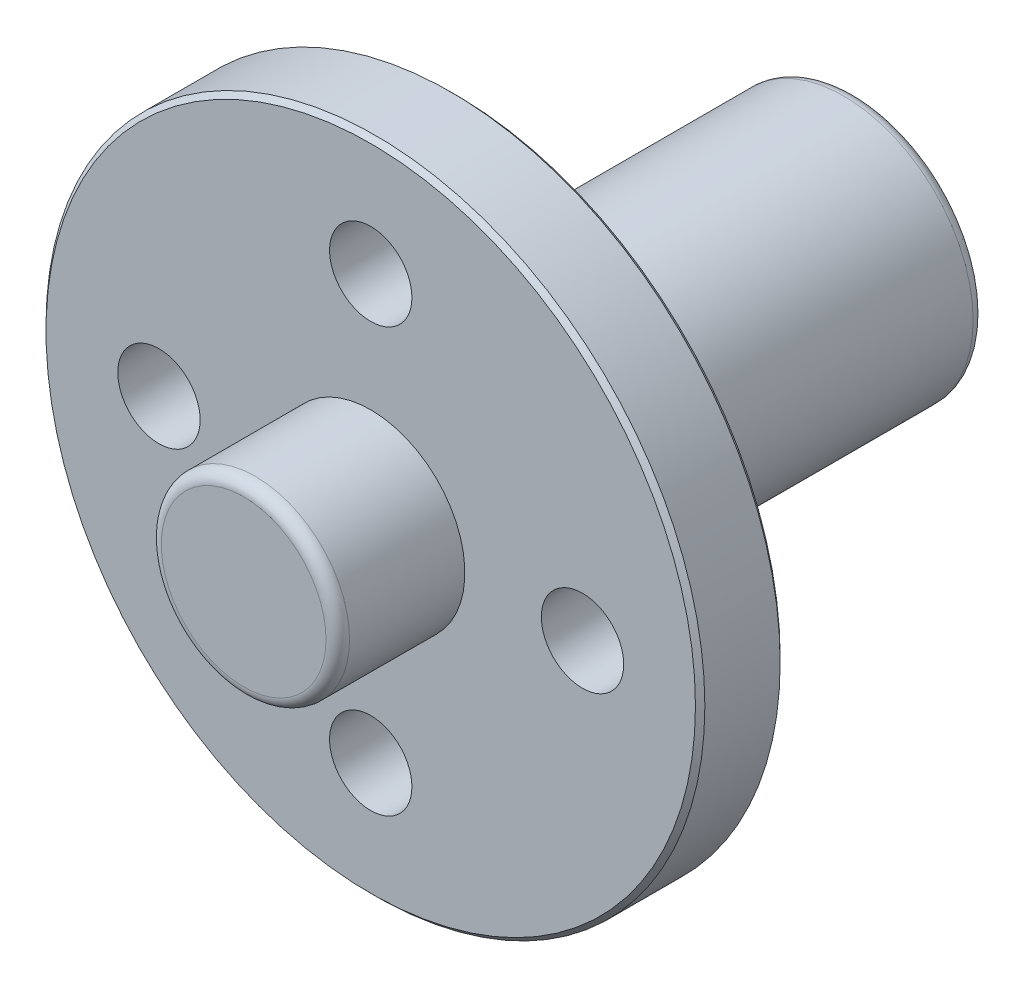
SolidWorks part; units mm, degrees
ref_plane "Front Plane" through (0, 0, 0) normal (0, 0, 1) x (1, 0, 0)
ref_plane "Top Plane" through (0, 0, 0) normal (0, 1, 0) x (1, 0, 0)
ref_plane "Right Plane" through (0, 0, 0) normal (1, 0, 0) x (0, 0, -1)
sketch "Sketch1" plane through (0, 0, 0) normal (0, 0, 1) x (1, 0, 0)
  circle A0 centre (0, 0) radius 14
  dimension "D1" = 28
extrude "Boss-Extrude1" add sketch "Sketch1" along normal blind 3.6
sketch "Sketch2" plane through (0, 0, 3.6) normal (0, 0, 1) x (1, 0, 0)
  circle A0 centre (0, 0) radius 4
  dimension "D1" = 8
extrude "Boss-Extrude2" add sketch "Sketch2" along normal blind 5.4
sketch "Sketch3" plane through (0, 0, 0) normal (0, 0, -1) x (-1, 0, 0)
  circle A0 centre (0, 0) radius 5.5
  dimension "D1" = 11
extrude "Boss-Extrude3" add sketch "Sketch3" along normal blind 17
sketch "Sketch4" plane through (0, 0, -17) normal (0, 0, -1) x (-1, 0, 0)
  circle A0 centre (0, 0) radius 3.5
  dimension "D1" = 7
extrude "Cut-Extrude1" cut sketch "Sketch4" against normal blind 17
sketch "Sketch5" plane through (0, 0, 0) normal (0, 0, -1) x (-1, 0, 0)
  line L0 (0, 9) -> (0, 0) construction
  circle A0 centre (0, 9) radius 1.75
  dimension "D2" = 3.5
  dimension "D1" = 9
extrude "Cut-Extrude2" cut sketch "Sketch5" against normal through all
pattern_circular "CirPattern1" count 4 every 90 about axis through (0, 0, 0) along (0, 0, -1) of "Cut-Extrude2"
sketch "Sketch6" plane through (0, 0, 0) normal (0, 1, 0) x (1, 0, 0)
  line L0 (0, 17) -> (0, 11) construction
  line L1 (3.5, 17) -> (-3.5, 17) construction
  circle A0 centre (0, 11) radius 1.75
  dimension "D2" = 3.5
  dimension "D1" = 6
extrude "Cut-Extrude3" cut sketch "Sketch6" against normal through all
fillet "Fillet1" radius 0.5 2 edges at (-5.5, 0, -17) (4, 0, 9)
fillet "Fillet2" radius 0.2 2 edges at (14, 0, 0) (14, 0, 3.6) profile chamfer
